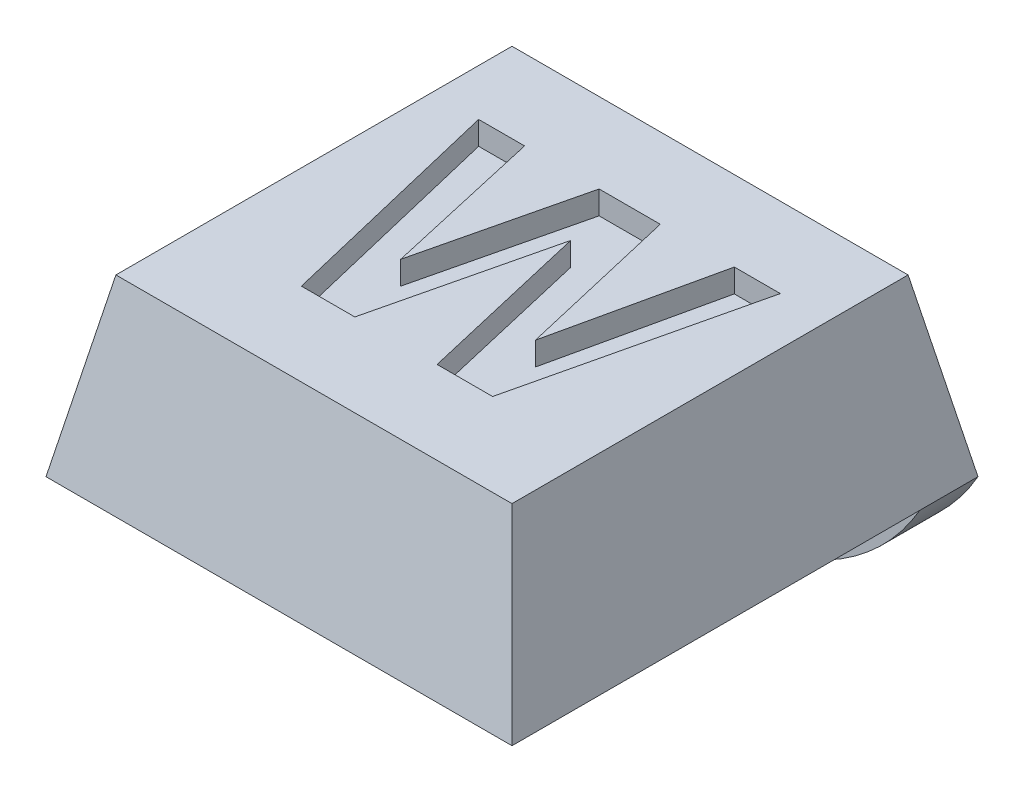
SolidWorks part; units mm, degrees
ref_plane "Front Plane" through (0, 0, 0) normal (0, 0, 1) x (1, 0, 0)
ref_plane "Top Plane" through (0, 0, 0) normal (0, 1, 0) x (1, 0, 0)
ref_plane "Right Plane" through (0, 0, 0) normal (1, 0, 0) x (0, 0, -1)
sketch "Sketch1" plane through (0, 0, 0) normal (0, 1, 0) x (1, 0, 0)
  line L1 (0, 0) -> (8, 0)
  line L2 (0, 0) -> (0, 8)
  line L3 (0, 8) -> (8, 8)
  line L4 (8, 0) -> (8, 8)
  dimension "D1" = 8
  dimension "D2" = 8
extrude "Boss-Extrude1" add sketch "Sketch1" along normal blind 3
sketch "Sketch2" plane through (0, 0, 0) normal (0, 0, 1) x (1, 0, 0)
  line L0 (0, 0) -> (0.6, 3)
  line L1 (0, 3) -> (8, 3) construction
  line L2 (0.6, 3) -> (0, 3)
  line L3 (0, 3) -> (0, 0)
  line L4 (8, 0) -> (7.4, 3)
  line L5 (7.4, 3) -> (8, 3)
  line L6 (8, 3) -> (8, 0)
  dimension "D1" = 0.6
  dimension "D2" = 0.6
extrude "Cut-Extrude1" cut sketch "Sketch2" against normal through all both and the other way through all
sketch "Sketch3" plane through (0, 0, 0) normal (1, 0, 0) x (0, 0, -1)
  line L0 (0, 0) -> (0.6, 3)
  line L1 (8, 3) -> (0, 3) construction
  line L2 (0.6, 3) -> (0, 3)
  line L3 (0, 3) -> (0, 0)
  line L4 (8, 3) -> (7.4, 3)
  line L5 (7.4, 3) -> (8, 0)
  line L6 (8, 3) -> (8, 0)
  dimension "D1" = 0.6
  dimension "D2" = 0.6
extrude "Cut-Extrude2" cut sketch "Sketch3" along normal blind 11
sketch "Sketch4" plane through (0, 0, 0) normal (0, -1, 0) x (1, 0, 0)
  line L0 (8, 0) -> (8, -8) construction
  line L3 (0, 0) -> (8, 0) construction
  circle A0 centre (4, -3.75) radius 1.8
  dimension "D1" = 3.6
  dimension "D2" = 4
  dimension "D3" = 3.75
extrude "Cut-Extrude3" cut sketch "Sketch4" against normal blind 0.8
sketch "Sketch5" plane through (0, 0, 0) normal (0, -1, 0) x (1, 0, 0)
  line L0 (8, 0) -> (8, -8) construction
  line L1 (0, -8) -> (8, -8)
  line L2 (0, -8) -> (0, -7)
  line L3 (0, -7) -> (8, -7)
  line L4 (8, -8) -> (8, -7)
  dimension "D1" = 1
extrude "Boss-Extrude2" add sketch "Sketch5" along normal blind 2
fillet "Fillet1" radius 4 2 edges at (8, -2, -7.5) (0, -2, -7.5)
sketch "Sketch6" plane through (0, 3, 0) normal (0, 1, 0) x (1, 0, 0)
  text T0 "W" font "Arial" height 4
extrude "Cut-Extrude4" cut sketch "Sketch6" against normal blind 0.4
